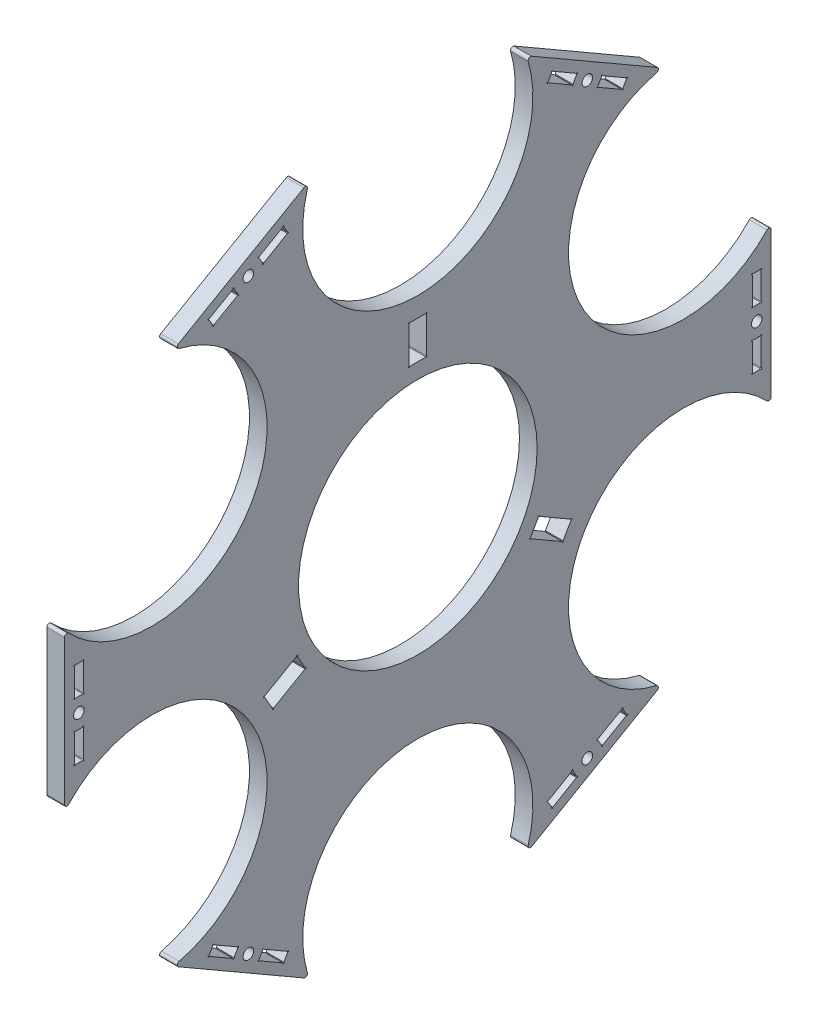
SolidWorks part; units mm, degrees
ref_plane "Front Plane" through (0, 0, 0) normal (0, 0, 1) x (1, 0, 0)
ref_plane "Top Plane" through (0, 0, 0) normal (0, 1, 0) x (1, 0, 0)
ref_plane "Right Plane" through (0, 0, 0) normal (1, 0, 0) x (0, 0, -1)
sketch "Sketch2" plane through (0, 0, 0) normal (1, 0, 0) x (0, 0, -1)
  line L0 (35.921, 114.3) -> (-35.921, 114.3) construction
  line L1 (81.0262, 88.2585) -> (35.921, 114.3)
  line L2 (116.9472, -26.0415) -> (116.9472, 26.0415)
  line L3 (35.921, -114.3) -> (81.0262, -88.2585)
  line L4 (-81.0262, -88.2585) -> (-35.921, -114.3)
  line L5 (-116.9472, 26.0415) -> (-116.9472, -26.0415)
  line L6 (-35.921, 114.3) -> (-81.0262, 88.2585)
  circle A0 centre (0, 0) radius 101.6 construction
  arc A1 (-35.921, 114.3) -> (35.921, 114.3) centre (0, 101.6) ccw
  arc A2 (81.0262, 88.2585) -> (116.9472, 26.0415) centre (87.9882, 50.8) ccw
  arc A3 (116.9472, -26.0415) -> (81.0262, -88.2585) centre (87.9882, -50.8) ccw
  arc A4 (35.921, -114.3) -> (-35.921, -114.3) centre (0, -101.6) ccw
  arc A5 (-81.0262, -88.2585) -> (-116.9472, -26.0415) centre (-87.9882, -50.8) ccw
  arc A6 (-116.9472, 26.0415) -> (-81.0262, 88.2585) centre (-87.9882, 50.8) ccw
  circle A7 centre (0, 0) radius 39.4875
  point P23 (0, 0)
  point P34 (0, 0)
  dimension "D1" = 203.2
  dimension "D2" = 114.3
  dimension "D3" = 76.2
  dimension "D6" = 78.9749
  dimension "D4" = 6
  dimension "D5" = 6
extrude "Boss-Extrude1" add sketch "Sketch2" along normal blind 5.842 contours A6 L5 A5 L4 A4 L3 A3 L2 A2 L1 A1 L6 region at (0, 30.1147, -52.1602)
fillet "Fillet1" radius 0.7937 12 edges at (2.921, -114.3, 35.921) (2.921, -114.3, -35.921) (2.921, -88.2585, -81.0262) (2.921, -26.0415, -116.9472) (2.921, 88.2585, -81.0262) (2.921, 26.0415, -116.9472) (2.921, -88.2585, 81.0262) (2.921, -26.0415, 116.9472) (2.921, 26.0415, 116.9472) (2.921, 88.2585, 81.0262) (2.921, 114.3, -35.921) (2.921, 114.3, 35.921)
sketch "Sketch3" plane through (5.842, 0, 0) normal (1, 0, 0) x (0, 0, -1)
  line L0 (0, 0) -> (0, 50.8) construction
  line L2 (6.1516, 53.721) -> (-6.1516, 53.721)
  line L3 (6.35, 53.5226) -> (6.35, 48.0774)
  line L4 (6.1516, 47.879) -> (-6.1516, 47.879)
  line L5 (-6.35, 53.5226) -> (-6.35, 48.0774)
  line L6 (6.35, 53.721) -> (-6.35, 47.879) construction
  line L7 (6.35, 47.879) -> (-6.35, 53.721) construction
  arc A0 (-6.1516, 53.721) -> (-6.35, 53.5226) centre (-6.35, 53.721) ccw
  arc A1 (-6.35, 48.0774) -> (-6.1516, 47.879) centre (-6.35, 47.879) ccw
  arc A2 (6.1516, 47.879) -> (6.35, 48.0774) centre (6.35, 47.879) ccw
  arc A3 (6.35, 53.5226) -> (6.1516, 53.721) centre (6.35, 53.721) ccw
  dimension "D4" = 0.3969
  dimension "D5" = 0.3969
  dimension "D6" = 0.3969
  dimension "D7" = 0.3969
  dimension "D1" = 50.8
  dimension "D2" = 12.7
  dimension "D3" = 5.842
extrude "Cut-Extrude2" [suppressed] cut sketch "Sketch3" against normal through all
pattern_circular "CirPattern1" [suppressed] count 3 every 120 of bodies 112
sketch "Sketch4" plane through (5.842, 0, 0) normal (1, 0, 0) x (0, 0, -1)
  line L0 (47.9712, -31.0114) -> (50.8422, -26.0386)
  line L1 (2.871, 57.05) -> (-2.871, 57.05)
  line L2 (2.871, 57.05) -> (2.871, 44.55)
  line L3 (2.871, 44.55) -> (-2.871, 44.55)
  line L4 (-2.871, 57.05) -> (-2.871, 44.55)
  line L5 (2.871, 57.05) -> (-2.871, 44.55) construction
  line L6 (2.871, 44.55) -> (-2.871, 57.05) construction
  line L7 (47.9712, -31.0114) -> (37.1459, -24.7614)
  line L8 (37.1459, -24.7614) -> (40.0169, -19.7886)
  line L9 (50.8422, -26.0386) -> (40.0169, -19.7886)
  line L10 (47.9712, -31.0114) -> (40.0169, -19.7886) construction
  line L11 (37.1459, -24.7614) -> (50.8422, -26.0386) construction
  line L12 (-50.8422, -26.0386) -> (-47.9712, -31.0114)
  line L13 (-50.8422, -26.0386) -> (-40.0169, -19.7886)
  line L14 (-40.0169, -19.7886) -> (-37.1459, -24.7614)
  line L15 (-47.9712, -31.0114) -> (-37.1459, -24.7614)
  line L16 (-50.8422, -26.0386) -> (-37.1459, -24.7614) construction
  line L17 (-40.0169, -19.7886) -> (-47.9712, -31.0114) construction
  circle A0 centre (0, 0) radius 50.8 construction
  point P3 (0, 50.8)
  point P10 (43.9941, -25.4)
  point P15 (-43.9941, -25.4)
  point P20 (0, 0)
  dimension "D1" = 101.6
  dimension "D2" = 12.5
  dimension "D3" = 5.742
  dimension "D4" = 3
extrude "Cut-Extrude3" cut sketch "Sketch4" against normal through all
sketch "Sketch5" plane through (5.842, 0, 0) normal (1, 0, 0) x (0, 0, -1)
  line L0 (-2.871, 50.8) -> (2.871, 50.8) construction
  line L1 (-2.871, 57.05) -> (-2.871, 44.55) construction
  line L2 (2.871, 44.55) -> (2.871, 57.05) construction
  line L3 (45.4296, -22.9136) -> (42.5586, -27.8864) construction
  line L4 (-42.5586, -27.8864) -> (-45.4296, -22.9136) construction
  circle A0 centre (2.871, 57.05) radius 0.1984
  circle A1 centre (-2.871, 57.05) radius 0.1984
  circle A2 centre (-2.871, 44.55) radius 0.1984
  circle A3 centre (2.871, 44.55) radius 0.1984
  circle A4 centre (47.9712, -31.0114) radius 0.1984
  circle A5 centre (50.8422, -26.0386) radius 0.1984
  circle A6 centre (40.0169, -19.7886) radius 0.1984
  circle A7 centre (37.1459, -24.7614) radius 0.1984
  circle A8 centre (-50.8422, -26.0386) radius 0.1984
  circle A9 centre (-47.9712, -31.0114) radius 0.1984
  circle A10 centre (-37.1459, -24.7614) radius 0.1984
  circle A11 centre (-40.0169, -19.7886) radius 0.1984
  point P38 (0, 0)
  dimension "D1" = 0.3969
  dimension "D2" = 0.3969
  dimension "D3" = 3
extrude "Cut-Extrude4" cut sketch "Sketch5" against normal through all
sketch "Sketch6" plane through (5.842, 0, 0) normal (1, 0, 0) x (0, 0, -1)
  line L0 (-58.4736, 101.2793) -> (0, 0) construction
  line L1 (-37.7084, 113.2681) -> (-79.2388, 89.2905) construction
  line L2 (-32.1468, 110.9798) -> (-80.0379, 83.3298) construction
  line L3 (-67.7219, 88.7229) -> (-60.9606, 96.0618) construction
  line L4 (-59.4731, 93.4854) -> (-69.2094, 91.2993) construction
  line L5 (-67.5501, 88.8221) -> (-59.6449, 93.3861)
  line L6 (-67.8212, 88.8947) -> (-69.1102, 91.1274)
  line L7 (-59.5723, 93.6572) -> (-60.8613, 95.8899)
  line L8 (-69.0376, 91.3985) -> (-61.1324, 95.9626)
  line L9 (-51.2242, 98.2479) -> (-44.4628, 105.5868) construction
  line L10 (-42.9753, 103.0104) -> (-52.7117, 100.8243) construction
  line L11 (-44.6346, 105.4876) -> (-52.5398, 100.9235)
  line L12 (-51.3234, 98.4197) -> (-52.6124, 100.6524)
  line L13 (-43.0745, 103.1822) -> (-44.3636, 105.4149)
  line L14 (-43.1471, 102.9111) -> (-51.0523, 98.3471)
  line L15 (43.1471, 102.9111) -> (51.0523, 98.3471)
  line L16 (43.0745, 103.1822) -> (44.3636, 105.4149)
  line L17 (51.3234, 98.4197) -> (52.6124, 100.6524)
  line L18 (44.6346, 105.4876) -> (52.5398, 100.9235)
  line L19 (69.0376, 91.3985) -> (61.1324, 95.9626)
  line L20 (59.5723, 93.6572) -> (60.8613, 95.8899)
  line L21 (67.8212, 88.8947) -> (69.1102, 91.1274)
  line L22 (67.5501, 88.8221) -> (59.6449, 93.3861)
  line L23 (58.4736, 101.2793) -> (0, 0) construction
  line L24 (80.0379, 83.3298) -> (32.1468, 110.9798) construction
  line L25 (42.9753, 103.0104) -> (52.7117, 100.8243) construction
  line L26 (51.2242, 98.2479) -> (44.4628, 105.5868) construction
  line L27 (59.4731, 93.4854) -> (69.2094, 91.2993) construction
  line L28 (67.7219, 88.7229) -> (60.9606, 96.0618) construction
  line L29 (110.6972, 14.0891) -> (110.6972, 4.9609)
  line L30 (110.8957, 14.2875) -> (113.4738, 14.2875)
  line L31 (110.8957, 4.7625) -> (113.4738, 4.7625)
  line L32 (113.6722, 14.0891) -> (113.6722, 4.9609)
  line L33 (113.6722, -14.0891) -> (113.6722, -4.9609)
  line L34 (110.8957, -4.7625) -> (113.4738, -4.7625)
  line L35 (110.8957, -14.2875) -> (113.4738, -14.2875)
  line L36 (110.6972, -14.0891) -> (110.6972, -4.9609)
  line L37 (116.9472, 0) -> (0, 0) construction
  line L38 (112.1847, -27.65) -> (112.1847, 27.65) construction
  line L39 (110.6972, 14.2875) -> (113.6722, 4.7625) construction
  line L40 (110.6972, 4.7625) -> (113.6722, 14.2875) construction
  line L41 (110.6972, -4.7625) -> (113.6722, -14.2875) construction
  line L42 (110.6972, -14.2875) -> (113.6722, -4.7625) construction
  line L43 (67.5501, -88.8221) -> (59.6449, -93.3861)
  line L44 (67.8212, -88.8947) -> (69.1102, -91.1274)
  line L45 (59.5723, -93.6572) -> (60.8613, -95.8899)
  line L46 (69.0376, -91.3985) -> (61.1324, -95.9626)
  line L47 (44.6346, -105.4876) -> (52.5398, -100.9235)
  line L48 (51.3234, -98.4197) -> (52.6124, -100.6524)
  line L49 (43.0745, -103.1822) -> (44.3636, -105.4149)
  line L50 (43.1471, -102.9111) -> (51.0523, -98.3471)
  line L51 (58.4736, -101.2793) -> (0, 0) construction
  line L52 (32.1468, -110.9798) -> (80.0379, -83.3298) construction
  line L53 (67.7219, -88.7229) -> (60.9606, -96.0618) construction
  line L54 (59.4731, -93.4854) -> (69.2094, -91.2993) construction
  line L55 (51.2242, -98.2479) -> (44.4628, -105.5868) construction
  line L56 (42.9753, -103.0104) -> (52.7117, -100.8243) construction
  line L57 (-43.1471, -102.9111) -> (-51.0523, -98.3471)
  line L58 (-43.0745, -103.1822) -> (-44.3636, -105.4149)
  line L59 (-51.3234, -98.4197) -> (-52.6124, -100.6524)
  line L60 (-44.6346, -105.4876) -> (-52.5398, -100.9235)
  line L61 (-69.0376, -91.3985) -> (-61.1324, -95.9626)
  line L62 (-59.5723, -93.6572) -> (-60.8613, -95.8899)
  line L63 (-67.8212, -88.8947) -> (-69.1102, -91.1274)
  line L64 (-67.5501, -88.8221) -> (-59.6449, -93.3861)
  line L65 (-58.4736, -101.2793) -> (0, 0) construction
  line L66 (-80.0379, -83.3298) -> (-32.1468, -110.9798) construction
  line L67 (-42.9753, -103.0104) -> (-52.7117, -100.8243) construction
  line L68 (-51.2242, -98.2479) -> (-44.4628, -105.5868) construction
  line L69 (-59.4731, -93.4854) -> (-69.2094, -91.2993) construction
  line L70 (-67.7219, -88.7229) -> (-60.9606, -96.0618) construction
  line L71 (-110.6972, -14.0891) -> (-110.6972, -4.9609)
  line L72 (-110.8957, -14.2875) -> (-113.4738, -14.2875)
  line L73 (-110.8957, -4.7625) -> (-113.4738, -4.7625)
  line L74 (-113.6722, -14.0891) -> (-113.6722, -4.9609)
  line L75 (-113.6722, 14.0891) -> (-113.6722, 4.9609)
  line L76 (-110.8957, 4.7625) -> (-113.4738, 4.7625)
  line L77 (-110.8957, 14.2875) -> (-113.4738, 14.2875)
  line L78 (-110.6972, 14.0891) -> (-110.6972, 4.9609)
  line L79 (-116.9472, 0) -> (0, 0) construction
  line L80 (-112.1847, 27.65) -> (-112.1847, -27.65) construction
  line L81 (-110.6972, -14.2875) -> (-113.6722, -4.7625) construction
  line L82 (-110.6972, -4.7625) -> (-113.6722, -14.2875) construction
  line L83 (-110.6972, 4.7625) -> (-113.6722, 14.2875) construction
  line L84 (-110.6972, 14.2875) -> (-113.6722, 4.7625) construction
  arc A0 (-44.3636, 105.4149) -> (-44.6346, 105.4876) centre (-44.4628, 105.5868) ccw
  arc A1 (-43.1471, 102.9111) -> (-43.0745, 103.1822) centre (-42.9753, 103.0104) ccw
  arc A2 (-51.3234, 98.4197) -> (-51.0523, 98.3471) centre (-51.2242, 98.2479) ccw
  arc A3 (-52.5398, 100.9235) -> (-52.6124, 100.6524) centre (-52.7117, 100.8243) ccw
  arc A4 (-61.1324, 95.9626) -> (-60.8613, 95.8899) centre (-60.9606, 96.0618) cw
  arc A5 (-59.5723, 93.6572) -> (-59.6449, 93.3861) centre (-59.4731, 93.4854) cw
  arc A6 (-67.5501, 88.8221) -> (-67.8212, 88.8947) centre (-67.7219, 88.7229) cw
  arc A7 (-69.1102, 91.1274) -> (-69.0376, 91.3985) centre (-69.2094, 91.2993) cw
  arc A8 (69.1102, 91.1274) -> (69.0376, 91.3985) centre (69.2094, 91.2993) ccw
  arc A9 (67.5501, 88.8221) -> (67.8212, 88.8947) centre (67.7219, 88.7229) ccw
  arc A10 (59.5723, 93.6572) -> (59.6449, 93.3861) centre (59.4731, 93.4854) ccw
  arc A11 (61.1324, 95.9626) -> (60.8613, 95.8899) centre (60.9606, 96.0618) ccw
  arc A12 (52.5398, 100.9235) -> (52.6124, 100.6524) centre (52.7117, 100.8243) cw
  arc A13 (51.3234, 98.4197) -> (51.0523, 98.3471) centre (51.2242, 98.2479) cw
  arc A14 (43.1471, 102.9111) -> (43.0745, 103.1822) centre (42.9753, 103.0104) cw
  arc A15 (44.3636, 105.4149) -> (44.6346, 105.4876) centre (44.4628, 105.5868) cw
  arc A16 (113.4738, -14.2875) -> (113.6722, -14.0891) centre (113.6722, -14.2875) ccw
  arc A17 (110.6972, -14.0891) -> (110.8957, -14.2875) centre (110.6972, -14.2875) ccw
  arc A18 (110.8957, -4.7625) -> (110.6972, -4.9609) centre (110.6972, -4.7625) ccw
  arc A19 (113.6722, -4.9609) -> (113.4738, -4.7625) centre (113.6722, -4.7625) ccw
  arc A20 (113.6722, 4.9609) -> (113.4738, 4.7625) centre (113.6722, 4.7625) cw
  arc A21 (110.8957, 4.7625) -> (110.6972, 4.9609) centre (110.6972, 4.7625) cw
  arc A22 (110.6972, 14.0891) -> (110.8957, 14.2875) centre (110.6972, 14.2875) cw
  arc A23 (113.4738, 14.2875) -> (113.6722, 14.0891) centre (113.6722, 14.2875) cw
  arc A24 (44.3636, -105.4149) -> (44.6346, -105.4876) centre (44.4628, -105.5868) ccw
  arc A25 (43.1471, -102.9111) -> (43.0745, -103.1822) centre (42.9753, -103.0104) ccw
  arc A26 (51.3234, -98.4197) -> (51.0523, -98.3471) centre (51.2242, -98.2479) ccw
  arc A27 (52.5398, -100.9235) -> (52.6124, -100.6524) centre (52.7117, -100.8243) ccw
  arc A28 (61.1324, -95.9626) -> (60.8613, -95.8899) centre (60.9606, -96.0618) cw
  arc A29 (59.5723, -93.6572) -> (59.6449, -93.3861) centre (59.4731, -93.4854) cw
  arc A30 (67.5501, -88.8221) -> (67.8212, -88.8947) centre (67.7219, -88.7229) cw
  arc A31 (69.1102, -91.1274) -> (69.0376, -91.3985) centre (69.2094, -91.2993) cw
  arc A32 (-69.1102, -91.1274) -> (-69.0376, -91.3985) centre (-69.2094, -91.2993) ccw
  arc A33 (-67.5501, -88.8221) -> (-67.8212, -88.8947) centre (-67.7219, -88.7229) ccw
  arc A34 (-59.5723, -93.6572) -> (-59.6449, -93.3861) centre (-59.4731, -93.4854) ccw
  arc A35 (-61.1324, -95.9626) -> (-60.8613, -95.8899) centre (-60.9606, -96.0618) ccw
  arc A36 (-52.5398, -100.9235) -> (-52.6124, -100.6524) centre (-52.7117, -100.8243) cw
  arc A37 (-51.3234, -98.4197) -> (-51.0523, -98.3471) centre (-51.2242, -98.2479) cw
  arc A38 (-43.1471, -102.9111) -> (-43.0745, -103.1822) centre (-42.9753, -103.0104) cw
  arc A39 (-44.3636, -105.4149) -> (-44.6346, -105.4876) centre (-44.4628, -105.5868) cw
  arc A40 (-113.4738, 14.2875) -> (-113.6722, 14.0891) centre (-113.6722, 14.2875) ccw
  arc A41 (-110.6972, 14.0891) -> (-110.8957, 14.2875) centre (-110.6972, 14.2875) ccw
  arc A42 (-110.8957, 4.7625) -> (-110.6972, 4.9609) centre (-110.6972, 4.7625) ccw
  arc A43 (-113.6722, 4.9609) -> (-113.4738, 4.7625) centre (-113.6722, 4.7625) ccw
  arc A44 (-113.6722, -4.9609) -> (-113.4738, -4.7625) centre (-113.6722, -4.7625) cw
  arc A45 (-110.8957, -4.7625) -> (-110.6972, -4.9609) centre (-110.6972, -4.7625) cw
  arc A46 (-110.6972, -14.0891) -> (-110.8957, -14.2875) centre (-110.6972, -14.2875) cw
  arc A47 (-113.4738, -14.2875) -> (-113.6722, -14.0891) centre (-113.6722, -14.2875) cw
  circle A48 centre (-56.0924, 97.1548) radius 1.7526
  circle A49 centre (56.0924, 97.1548) radius 1.7526
  circle A50 centre (112.1847, 0) radius 1.7526
  circle A51 centre (56.0924, -97.1548) radius 1.7526
  circle A52 centre (-56.0924, -97.1548) radius 1.7526
  circle A53 centre (-112.1847, 0) radius 1.7526
  point P8 (-56.0924, 97.1548)
  point P9 (-56.0924, 97.1548)
  point P18 (-47.8435, 101.9173)
  point P34 (-64.3412, 92.3923)
  point P41 (56.0924, 97.1548)
  point P42 (56.0924, 97.1548)
  point P51 (64.3412, 92.3923)
  point P67 (47.8435, 101.9173)
  point P72 (112.1847, 0)
  point P73 (112.1847, 0)
  point P82 (112.1847, -9.525)
  point P98 (112.1847, 9.525)
  point P103 (56.0924, -97.1548)
  point P104 (56.0924, -97.1548)
  point P113 (47.8435, -101.9173)
  point P129 (64.3412, -92.3923)
  point P134 (-56.0924, -97.1548)
  point P135 (-56.0924, -97.1548)
  point P144 (-64.3412, -92.3923)
  point P160 (-47.8435, -101.9173)
  point P165 (-112.1847, 0)
  point P166 (-112.1847, 0)
  point P175 (-112.1847, 9.525)
  point P191 (-112.1847, -9.525)
  point P192 (0, 0)
  point P205 (0, 0)
  dimension "D5" = 0.3969
  dimension "D6" = 0.3969
  dimension "D7" = 0.3969
  dimension "D8" = 0.3969
  dimension "D4" = 3.5052
  dimension "D1" = 4.7625
  dimension "D2" = 9.525
  dimension "D3" = 6
  dimension "D9" = 6
extrude "Cut-Extrude5" cut sketch "Sketch6" against normal through all
